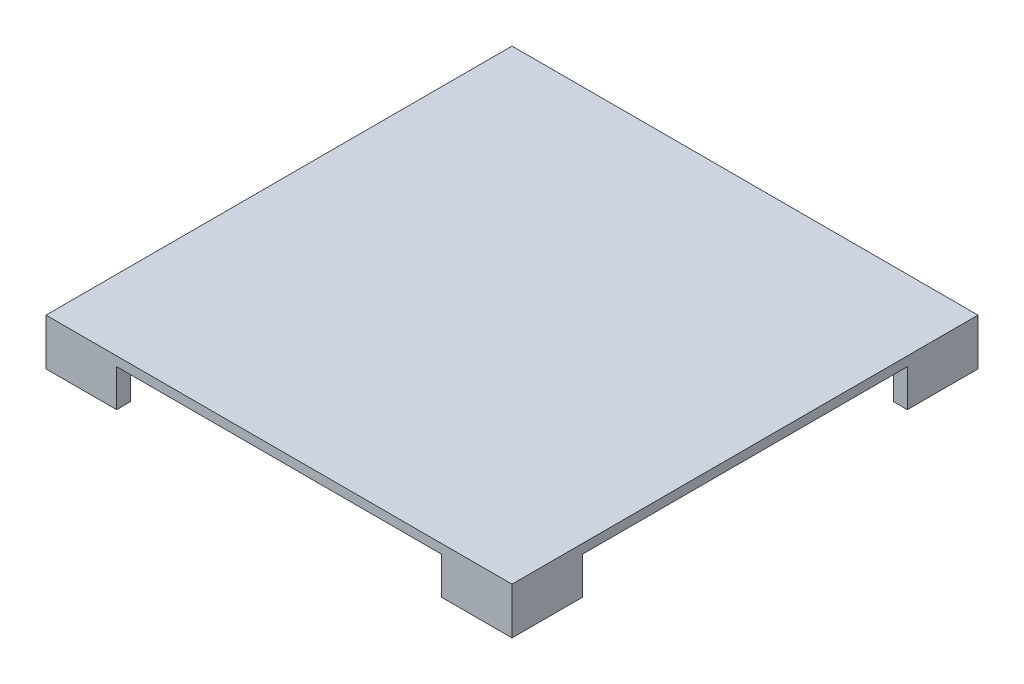
SolidWorks part; units mm, degrees
ref_plane "Front Plane" through (0, 0, 0) normal (0, 0, 1) x (1, 0, 0)
ref_plane "Top Plane" through (0, 0, 0) normal (0, 1, 0) x (1, 0, 0)
ref_plane "Right Plane" through (0, 0, 0) normal (1, 0, 0) x (0, 0, -1)
sketch "Sketch2" plane through (0, 0, 0) normal (0, 1, 0) x (1, 0, 0)
  line L0 (0, 0) -> (0, 250) construction
  line L1 (-250, -250) -> (250, -250)
  line L2 (-250, -250) -> (-250, 250)
  line L3 (-250, 250) -> (250, 250)
  line L4 (250, -250) -> (250, 250)
  line L5 (-250, -250) -> (250, 250) construction
  line L6 (-250, 250) -> (250, -250) construction
  line L7 (-250, 250) -> (-174.2506, 250)
  line L8 (-250, 250) -> (-250, 216.633)
  line L9 (-235, 235) -> (-174.2506, 235)
  line L10 (-174.2506, 250) -> (-174.2506, 235)
  line L11 (-250, 250) -> (-216.633, 250)
  line L12 (-250, 250) -> (-250, 174.2506)
  line L13 (-250, 174.2506) -> (-235, 174.2506)
  line L14 (-235, 235) -> (-235, 174.2506)
  line L15 (0, 0) -> (-250, 0) construction
  line L16 (174.2506, 250) -> (174.2506, 235)
  line L17 (235, 235) -> (174.2506, 235)
  line L18 (235, 235) -> (235, 174.2506)
  line L19 (250, 174.2506) -> (235, 174.2506)
  line L20 (-174.2506, -250) -> (-174.2506, -235)
  line L21 (-235, -235) -> (-174.2506, -235)
  line L22 (-235, -235) -> (-235, -174.2506)
  line L23 (-250, -174.2506) -> (-235, -174.2506)
  line L24 (250, -174.2506) -> (235, -174.2506)
  line L25 (235, -235) -> (235, -174.2506)
  line L26 (235, -235) -> (174.2506, -235)
  line L27 (174.2506, -250) -> (174.2506, -235)
  point P1 (0, 0)
  dimension "D1" = 15
  dimension "D2" = 500
  dimension "D3" = 500
extrude "Boss-Extrude1" add sketch "Sketch2" along normal blind 10 contours L1 L27 L26 L25 L24 L4 L19 L18 L17 L16 L3 L10 L9 L14 L13 L2 L23 L22 L21 L20 | L27 L1 L4 L24 L25 L26 | L23 L2 L1 L20 L21 L22 | L14 L9 L10 L7 L3 L2 L13 | L19 L4 L3 L16 L17 L18 region at (-248.9287, 0, 212.1253) region at (0, 0, 0) region at (175.3219, 0, 242.5) region at (-248.9287, 0, -195.4418) region at (242.5, 0, -175.3219)
extrude "Boss-Extrude2" add sketch "Sketch2<3>" against normal blind 40 contours L19 L4 L3 L16 L17 L18 | L23 L2 L1 L20 L21 L22 | L14 L9 L10 L7 L3 L2 L13 | L27 L1 L4 L24 L25 L26 region at (-248.9287, 0, 212.1253) region at (175.3219, 0, 242.5) region at (-248.9287, 0, -195.4418) region at (242.5, 0, -175.3219)
sketch "Sketch2<3>" plane through (0, 0, 0) normal (0, 1, 0) x (1, 0, 0) same geometry as "Sketch2"
